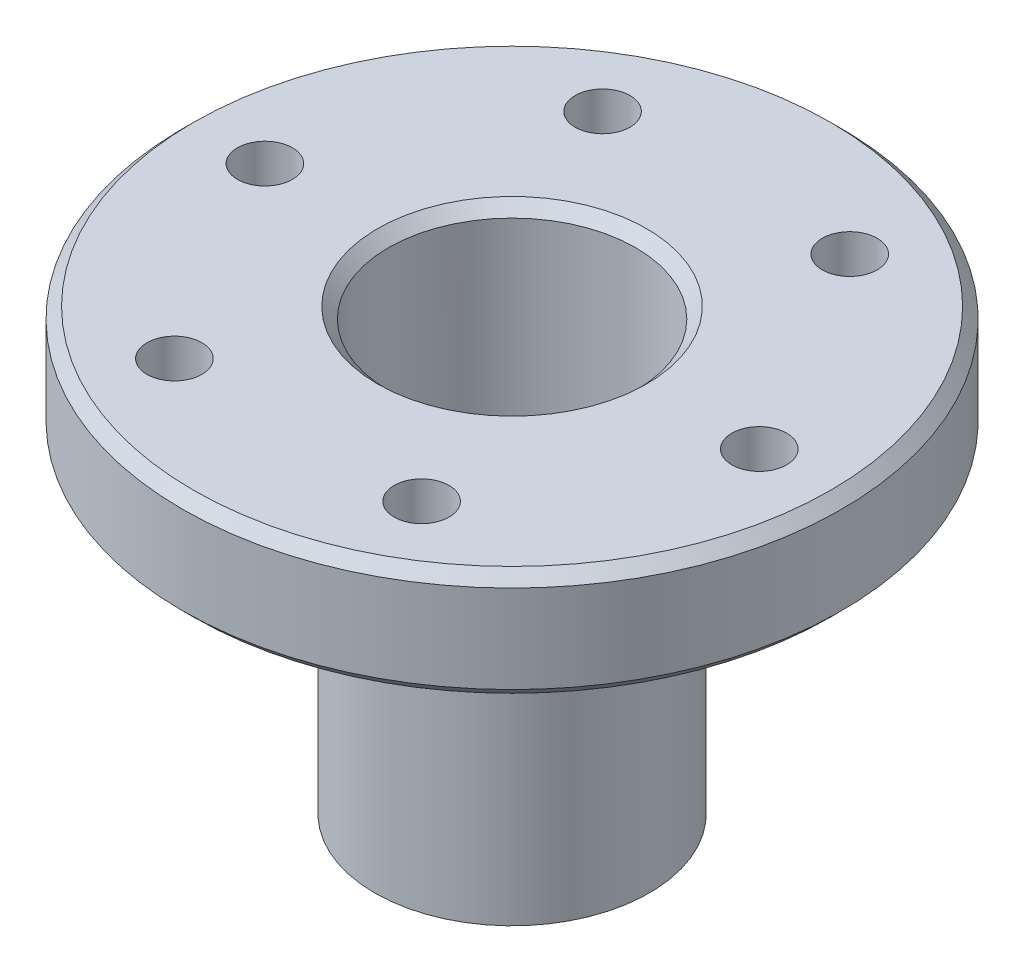
SolidWorks part; units mm, degrees
ref_plane "Front Plane" through (0, 0, 0) normal (0, 0, 1) x (1, 0, 0)
ref_plane "Top Plane" through (0, 0, 0) normal (0, 1, 0) x (1, 0, 0)
ref_plane "Right Plane" through (0, 0, 0) normal (1, 0, 0) x (0, 0, -1)
sketch "Sketch2" plane through (0, 0, 0) normal (0, 1, 0) x (1, 0, 0)
  line L0 (-69.4747, 0) -> (69.4747, 0) construction
  line L1 (0, -73.6995) -> (0, 73.6995) construction
  circle A0 centre (0, 0) radius 22.5
  circle A1 centre (0, 0) radius 45 construction
  circle A2 centre (0, 0) radius 60
  circle A3 centre (45, 0) radius 5
  circle A4 centre (22.5, -38.9711) radius 5
  circle A5 centre (-22.5, -38.9711) radius 5
  circle A6 centre (-45, 0) radius 5
  circle A7 centre (-22.5, 38.9711) radius 5
  circle A8 centre (22.5, 38.9711) radius 5
  point P8 (0, 0)
  point P11 (0, 0)
  point P26 (0, 0)
  dimension "D1" = 120
  dimension "D2" = 90
  dimension "D3" = 45
  dimension "D4" = 10
  dimension "D5" = 6
extrude "Boss-Extrude1" add sketch "Sketch2" along normal blind 20
chamfer "Chamfer1" distance 2 angle 45 1 edges at (0, 20, 60)
chamfer "Chamfer2" distance 2 angle 45 1 edges at (0, 20, 22.5)
sketch "Sketch3" plane through (0, 0, 0) normal (0, -1, 0) x (-1, 0, 0)
  circle A0 centre (0, 0) radius 25
  dimension "D1" = 50
extrude "Boss-Extrude2" add sketch "Sketch3" along normal blind 60
fillet "Fillet1" radius 3 1 edges at (0, 0, 25)
extrude "Cut-Extrude1" cut sketch "Sketch2<2>" against normal blind 60 contours A0 region at (0, 0, 0)
sketch "Sketch2<2>" plane through (0, 0, 0) normal (0, 1, 0) x (1, 0, 0) same geometry as "Sketch2"
chamfer "Chamfer3" distance 2 angle 45 1 edges at (0, -60, 22.5)
chamfer "Chamfer4" distance 2 angle 45 1 edges at (0, 0, 60)
